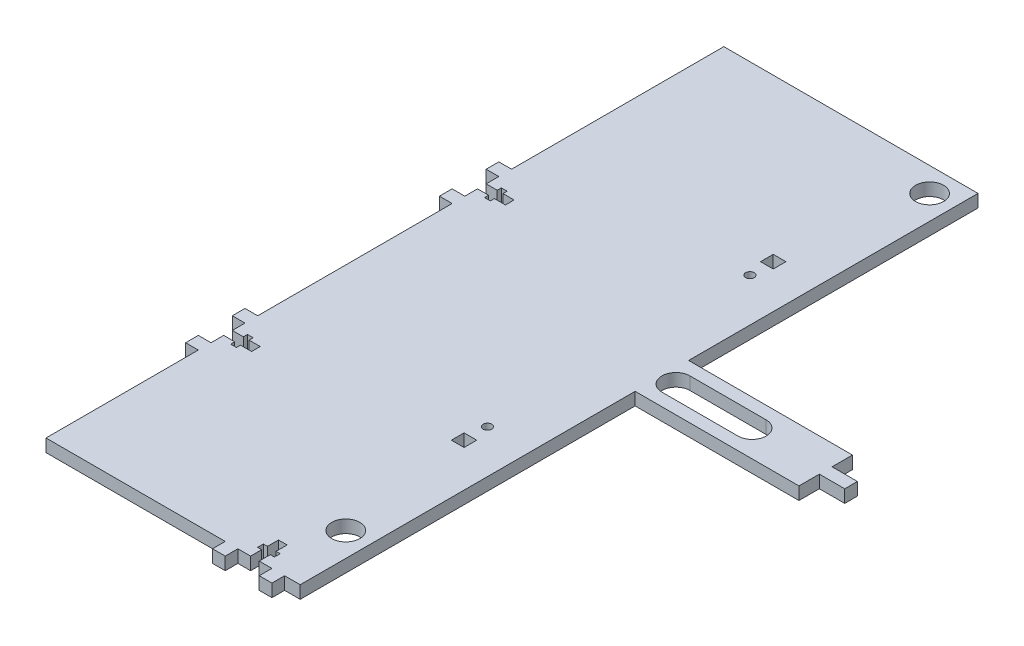
SolidWorks part; units mm, degrees
ref_plane "Front Plane" through (0, 0, 0) normal (0, 0, 1) x (1, 0, 0)
ref_plane "Top Plane" through (0, 0, 0) normal (0, 1, 0) x (1, 0, 0)
ref_plane "Right Plane" through (0, 0, 0) normal (1, 0, 0) x (0, 0, -1)
sketch "Axle Support Plate" plane through (0, 0, 0) normal (0, 1, 0) x (1, 0, 0)
  line L0 (25.4, 146.05) -> (25.4, -146.05) construction
  line L1 (12.7, 158.1601) -> (12.7, -187.325) construction
  line L2 (12.7, -80.518) -> (12.7, -74.168)
  line L3 (12.7, 80.518) -> (19.05, 80.518)
  line L4 (37.5101, -180.975) -> (37.5101, -13.3801)
  line L5 (0, 0) -> (37.5101, 158.1601) construction
  line L6 (0, 0) -> (37.5101, -180.975) construction
  line L7 (-89.662, -75.057) -> (-89.662, 22.225)
  line L8 (-89.662, 158.1601) -> (37.5101, 158.1601)
  line L9 (6.35, -180.975) -> (12.7, -180.975)
  line L10 (12.7, 80.518) -> (12.7, 74.168)
  line L11 (12.7, 74.168) -> (19.05, 74.168)
  line L12 (0, -187.325) -> (0, -180.975)
  line L13 (19.05, 80.518) -> (19.05, 74.168)
  line L14 (12.7, -80.518) -> (19.05, -80.518)
  line L15 (19.05, -80.518) -> (19.05, -74.168)
  line L16 (12.7, -74.168) -> (19.05, -74.168)
  line L17 (37.5101, 0) -> (0, 0) construction
  line L18 (0, -187.325) -> (6.35, -187.325)
  line L19 (6.35, -187.325) -> (6.35, -180.975)
  line L20 (23.368, -180.975) -> (23.368, -187.325)
  line L21 (23.368, -187.325) -> (29.718, -187.325)
  line L22 (29.718, -187.325) -> (29.718, -180.975)
  line L23 (29.718, -180.975) -> (37.5101, -180.975)
  line L24 (15.875, 80.518) -> (15.875, 65.659) construction
  line L25 (12.7, -180.975) -> (12.7, -175.44)
  line L26 (12.7, -175.44) -> (10.659, -175.44)
  line L27 (10.659, -175.44) -> (10.659, -172.54)
  line L28 (10.659, -172.54) -> (12.7, -172.54)
  line L29 (12.7, -172.54) -> (12.7, -167.005)
  line L30 (12.7, -167.005) -> (17.018, -167.005)
  line L31 (17.018, -167.005) -> (17.018, -172.54)
  line L32 (17.018, -172.54) -> (19.059, -172.54)
  line L33 (19.059, -172.54) -> (19.059, -175.44)
  line L34 (19.059, -175.44) -> (17.018, -175.44)
  line L35 (17.018, -175.44) -> (17.018, -180.975)
  line L36 (17.018, -180.975) -> (23.368, -180.975)
  line L37 (37.5101, 13.3801) -> (119.4703, 13.3801)
  line L38 (119.4703, 13.3801) -> (119.4703, 3.175)
  line L39 (119.4703, -13.3801) -> (37.5101, -13.3801)
  line L40 (44.5403, 0) -> (82.6403, 0) construction
  line L41 (44.5403, 7.0301) -> (82.6403, 7.0301)
  line L42 (44.5403, -7.0301) -> (82.6403, -7.0301)
  line L43 (119.4703, -3.175) -> (132.1703, -3.175)
  line L44 (132.1703, -3.175) -> (132.1703, 3.175)
  line L45 (132.1703, 3.175) -> (119.4703, 3.175)
  line L46 (37.5101, 13.3801) -> (37.5101, 158.1601)
  line L47 (37.5101, 13.3801) -> (37.5101, -13.3801) construction
  line L48 (37.5101, 0) -> (132.1703, 0) construction
  line L51 (119.4703, -3.175) -> (119.4703, -13.3801)
  line L81 (-89.662, 51.943) -> (-89.662, 158.1601)
  line L90 (0, -180.975) -> (-89.662, -180.975)
  line L94 (-89.662, -180.975) -> (-89.662, -104.775)
  circle A0 centre (25.4, 146.05) radius 7.0301
  circle A1 centre (25.4, -146.05) radius 7.0301
  circle A2 centre (15.875, 65.659) radius 2.159
  circle A3 centre (15.875, -65.659) radius 2.159
  arc A4 (44.5403, 7.0301) -> (44.5403, -7.0301) centre (44.5403, 0) ccw
  arc A5 (82.6403, -7.0301) -> (82.6403, 7.0301) centre (82.6403, 0) ccw
  point P0 (0, 0)
  point P15 (25.4, 0)
  point P38 (15.875, 67.818)
  point P57 (63.5903, 0)
  line B0 (-89.662, -81.407) -> (-96.012, -81.407)
  line B1 (-96.012, -81.407) -> (-96.012, -75.057)
  line B2 (-96.012, -75.057) -> (-89.662, -75.057)
  line B3 (-89.662, -87.757) -> (-84.127, -87.757)
  line B4 (-84.127, -87.757) -> (-84.127, -85.716)
  line B5 (-84.127, -85.716) -> (-81.227, -85.716)
  line B6 (-81.227, -85.716) -> (-81.227, -87.757)
  line B7 (-81.227, -87.757) -> (-75.692, -87.757)
  line B8 (-75.692, -87.757) -> (-75.692, -92.075)
  line B9 (-75.692, -92.075) -> (-81.227, -92.075)
  line B10 (-81.227, -92.075) -> (-81.227, -94.116)
  line B11 (-81.227, -94.116) -> (-84.127, -94.116)
  line B12 (-84.127, -94.116) -> (-84.127, -92.075)
  line B13 (-84.127, -92.075) -> (-89.662, -92.075)
  line B14 (-75.692, -89.916) -> (-89.662, -89.916) construction
  line B15 (-89.662, -98.425) -> (-89.662, -92.075)
  line B16 (-96.012, -104.775) -> (-89.662, -104.775)
  line B17 (-89.662, -81.407) -> (-89.662, -87.757)
  line B18 (-96.012, -98.425) -> (-96.012, -104.775)
  line B19 (-89.662, -98.425) -> (-96.012, -98.425)
  line B20 (-89.662, 45.593) -> (-96.012, 45.593)
  line B21 (-96.012, 45.593) -> (-96.012, 51.943)
  line B22 (-96.012, 51.943) -> (-89.662, 51.943)
  line B23 (-89.662, 39.243) -> (-84.127, 39.243)
  line B24 (-84.127, 39.243) -> (-84.127, 41.284)
  line B25 (-84.127, 41.284) -> (-81.227, 41.284)
  line B26 (-81.227, 41.284) -> (-81.227, 39.243)
  line B27 (-81.227, 39.243) -> (-75.692, 39.243)
  line B28 (-75.692, 39.243) -> (-75.692, 34.925)
  line B29 (-75.692, 34.925) -> (-81.227, 34.925)
  line B30 (-81.227, 34.925) -> (-81.227, 32.884)
  line B31 (-81.227, 32.884) -> (-84.127, 32.884)
  line B32 (-84.127, 32.884) -> (-84.127, 34.925)
  line B33 (-84.127, 34.925) -> (-89.662, 34.925)
  line B34 (-75.692, 37.084) -> (-89.662, 37.084) construction
  line B35 (-89.662, 28.575) -> (-89.662, 34.925)
  line B36 (-96.012, 22.225) -> (-89.662, 22.225)
  line B37 (-89.662, 45.593) -> (-89.662, 39.243)
  line B38 (-96.012, 28.575) -> (-96.012, 22.225)
  line B39 (-89.662, 28.575) -> (-96.012, 28.575)
  dimension "D1" = 5.08
  dimension "D4" = 14.0603
  dimension "D5" = 5.08
  dimension "D8" = 63.5
  dimension "D14" = 14.0603
  dimension "D15" = 4.318
  dimension "D16" = 6.35
  dimension "D22" = 7.0301
  dimension "D25" = 36.83
  dimension "D2" = 292.1
  dimension "D3" = 6.35
  dimension "D6" = 12.7
  dimension "D7" = 6.35
  dimension "D9" = 12.7
  dimension "D10" = 6.35
  dimension "D11" = 6.35
  dimension "D12" = 13.97
  dimension "D13" = 34.925
  dimension "D17" = 4.318
  dimension "D18" = 8.4
  dimension "D19" = 2.9
  dimension "D20" = 6.35
  dimension "D21" = 6.35
  dimension "D23" = 6.35
  dimension "D24" = 38.1
  dimension "D26" = 12.7
  dimension "D27" = 6.35
  dimension "D28" = 89.662
  dimension "D29" = 76.2
  dimension "D30" = 203.2
sketch_block_instance "Male T-slot assembly-1"
sketch_block "Male T-slot assembly" parameters "D1"=6.35, "D2"=6.35, "D3"=4.318, "D4"=2.9, "D5"=8.4, "D6"=13.97, "D7"=6.35
sketch_block_instance "Male T-slot assembly-2"
extrude "Boss-Extrude1" add sketch "Axle Support Plate" along normal blind 6.35 contours L12 L18 L19 L9 L25 L26 L27 L28 L29 L30 L31 L32 L33 L34 L35 L36 L20 L21 L22 L23 L4 L39 L51 L43 L44 L45 L38 L37 L46 L8 region at (-22.538, 0, 11.1636)
equation "\"Ball Diameter\"= 1.75in"
equation "\"Sheet Thickness\"= 0.25in"
equation "\"Screw Diameter\"= .17in"
equation "\"Robot Diameter\"= 14in"
equation "\"Castor Screw Diameter\"= 0.22in"
equation "\"Wheel Diameter\" = 4in"
equation "\"Nut Diameter\" = 8.4mm"
equation "\"Nut Height\" = 2.9mm"
equation "\"Screw Height\" = 0.55in"
equation "\"Pulley Diameter\" = 1in"
equation "\"Reactor Height\" = 14in"
equation "\"Elevator Height\" = 11.5in"
equation "\"Elevator Width\" = \"Ball Diameter\" + 0.25in"
equation "\"D1@Boss-Extrude1\"=\"Sheet Thickness\""
equation "\"Elevator Bearing Diameter\" = sqr(2*(\"Sheet Thickness\"^2)) + 0.2in"
equation "\"Elevator Axle Length\" = \"Elevator Width\" + 8*\"Sheet Thickness\""
equation "\"D4@Axle Support Plate\"=\"Elevator Bearing Diameter\""
equation "\"D6@Axle Support Plate\"=(\"Pulley Diameter\")/2"
equation "\"D3@Axle Support Plate\"=\"Sheet Thickness\""
equation "\"D7@Axle Support Plate\"=\"Sheet Thickness\""
equation "\"D10@Axle Support Plate\"=\"Sheet Thickness\""
equation "\"D11@Axle Support Plate\"=\"Sheet Thickness\""
equation "\"D12@Axle Support Plate\"=\"Screw Height\""
equation "\"D13@Axle Support Plate\"=2.5in - \"Sheet Thickness\" - (\"Ball Diameter\")/2"
equation "\"D9@Axle Support Plate\"=2*\"Sheet Thickness\""
equation "\"D14@Axle Support Plate\"=\"Elevator Bearing Diameter\""
equation "\"D15@Axle Support Plate\"=\"Screw Diameter\""
equation "\"D16@Axle Support Plate\"=\"Sheet Thickness\""
equation "\"D17@Axle Support Plate\"=\"Screw Diameter\""
equation "\"D18@Axle Support Plate\"=\"Nut Diameter\""
equation "\"D19@Axle Support Plate\"=\"Nut Height\""
equation "\"D20@Axle Support Plate\"=\"Sheet Thickness\""
equation "\"D21@Axle Support Plate\"=\"Sheet Thickness\""
equation "\"D22@Axle Support Plate\"=\"Elevator Bearing Diameter\"/2"
equation "\"D23@Axle Support Plate\"=\"Sheet Thickness\""
equation "\"Elevator Axle Endcap Diameter\" = \"Pulley Diameter\" + 0.25in"
equation "\"D25@Axle Support Plate\"=\"Elevator Axle Endcap Diameter\"+0.2in"
equation "\"D27@Axle Support Plate\"=\"Sheet Thickness\""
equation "\"Elevator Clearance from Axis\" = 3.28in"
equation "\"D28@Axle Support Plate\"=\"Elevator Clearance from Axis\" + \"Sheet Thickness\""
